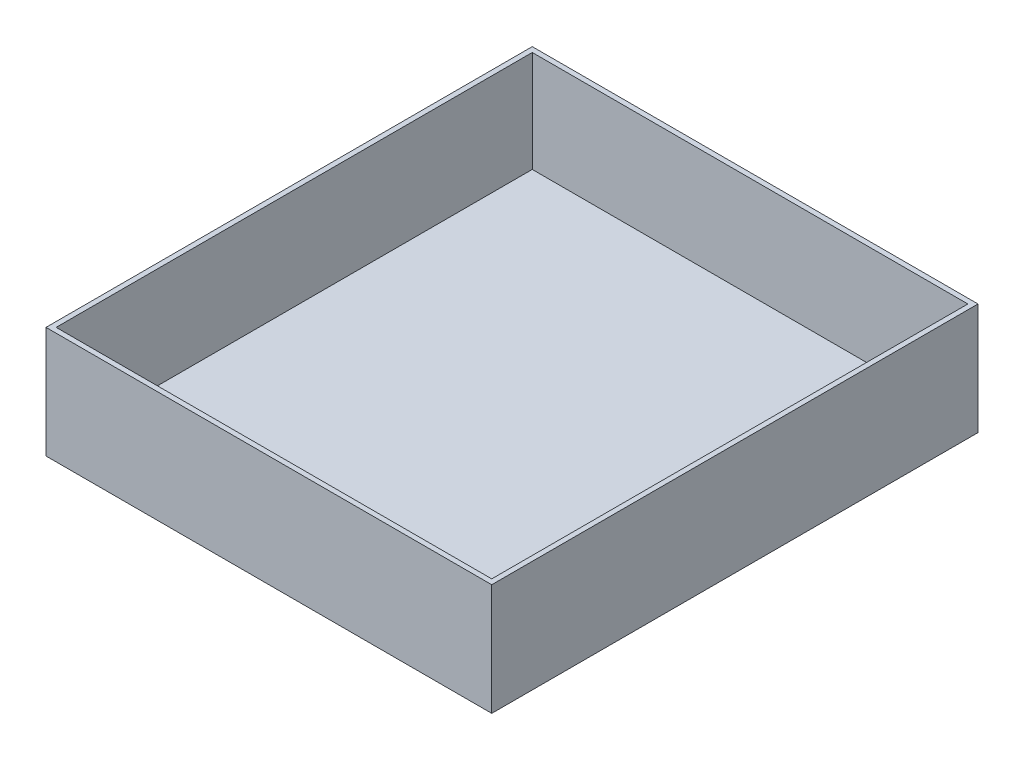
SolidWorks part; units mm, degrees
ref_plane "Front Plane" through (0, 0, 0) normal (0, 0, 1) x (1, 0, 0)
ref_plane "Top Plane" through (0, 0, 0) normal (0, 1, 0) x (1, 0, 0)
ref_plane "Right Plane" through (0, 0, 0) normal (1, 0, 0) x (0, 0, -1)
sketch "Sketch1" plane through (0, 0, 0) normal (0, 1, 0) x (1, 0, 0)
  line L1 (0, 0) -> (279.4, 0)
  line L2 (0, 0) -> (0, 304.8)
  line L3 (0, 304.8) -> (279.4, 304.8)
  line L4 (279.4, 0) -> (279.4, 304.8)
  dimension "D1" = 279.4
  dimension "D2" = 304.8
extrude "Boss-Extrude1" add sketch "Sketch1" along normal blind 69.85
sketch "Sketch3" plane through (0, 69.85, 0) normal (0, 1, 0) x (1, 0, 0)
  line L14 (3.175, 3.175) -> (276.225, 3.175)
  line L15 (276.225, 3.175) -> (276.225, 301.625)
  line L16 (3.175, 301.625) -> (3.175, 3.175)
  line L17 (276.225, 301.625) -> (3.175, 301.625)
  line L18 (3.175, 3.175) -> (276.225, 3.175)
  line L19 (276.225, 3.175) -> (276.225, 301.625)
  line L20 (3.175, 301.625) -> (3.175, 3.175)
  line L21 (276.225, 301.625) -> (3.175, 301.625)
  dimension "D1" = 3.175
extrude "Cut-Extrude1" cut sketch "Sketch3" against normal blind 63.5
